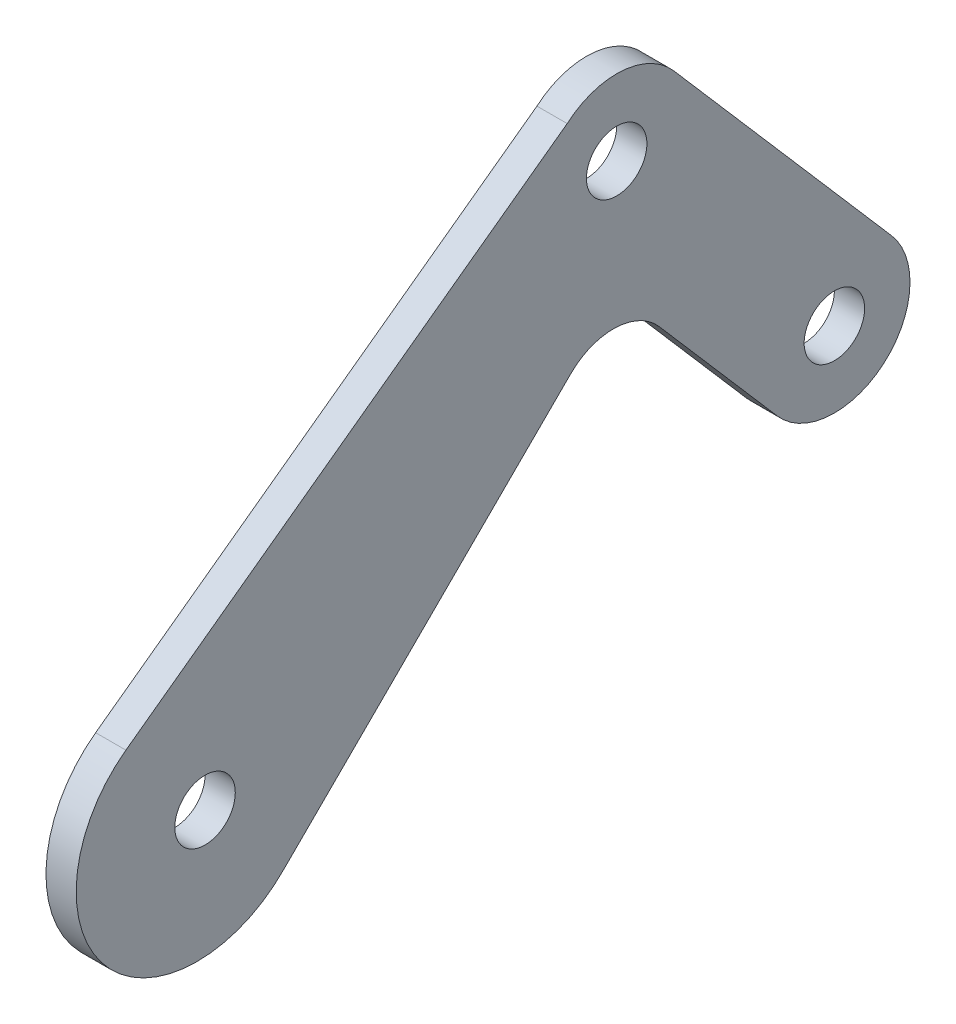
SolidWorks part; units mm, degrees
material "Alloy Steel"
ref_plane "Front Plane" through (0, 0, 0) normal (0, 0, 1) x (1, 0, 0)
ref_plane "Top Plane" through (0, 0, 0) normal (0, 1, 0) x (1, 0, 0)
ref_plane "Right Plane" through (0, 0, 0) normal (1, 0, 0) x (0, 0, -1)
sketch "Sketch1" plane through (0, 0, 0) normal (1, 0, 0) x (0, 0, -1)
  line L0 (0, 0) -> (-43.2126, -37.4005) construction
  line L1 (0, 0) -> (22.8559, -26.4077) construction
  line L2 (-43.2126, -37.4005) -> (-20.3567, -63.8082) construction
  line L3 (22.8559, -26.4077) -> (-20.3567, -63.8082) construction
  line L4 (16.8541, -31.6022) -> (4.4563, -17.2778)
  line L5 (22.8559, -26.4077) -> (58.3525, 4.3147) construction
  line L6 (28.8576, -21.2132) -> (6.0017, 5.1945)
  line L7 (-43.2126, -37.4005) -> (-76.3416, 0.8768) construction
  line L8 (-34.9587, -46.937) -> (-4.8255, -16.9336)
  line L9 (-5.1945, 6.0017) -> (-51.5238, -27.7977)
  line L10 (-61.3926, -16.3952) -> (-9.8123, 28.2476) construction
  line L11 (0, 0) -> (-18.1801, 21.0053) construction
  line L12 (0, 0) -> (22.5943, 19.5554) construction
  line L13 (-43.2126, -37.4005) -> (-62.0308, -52.3663) construction
  circle A0 centre (0, 0) radius 3.175
  circle A1 centre (22.8559, -26.4077) radius 3.175
  circle A2 centre (-43.2126, -37.4005) radius 3.175
  arc A3 (16.8541, -31.6022) -> (28.8576, -21.2132) centre (22.8559, -26.4077) ccw
  arc A4 (-51.5238, -27.7977) -> (-34.9587, -46.937) centre (-44.0387, -38.0575) ccw
  arc A5 (-5.1945, 6.0017) -> (6.0017, 5.1945) centre (0, 0) cw
  arc A6 (4.4563, -17.2778) -> (-4.8255, -16.9336) centre (-0.345, -21.4334) ccw
  point P26 (0, -12.1289)
  dimension "D3" = 6.35
  dimension "D6" = 12.7
  dimension "D10" = 6.35
  dimension "D8" = 7.9375
  dimension "D9" = 12.7
  dimension "D4" = 7.9375
  dimension "D1" = 34.925
  dimension "D2" = 57.15
  dimension "D5" = 21.4334
  dimension "D7" = 4
  dimension "D11" = 43.7607
extrude "Boss-Extrude1" add sketch "Sketch1" along normal mid plane 3.175
